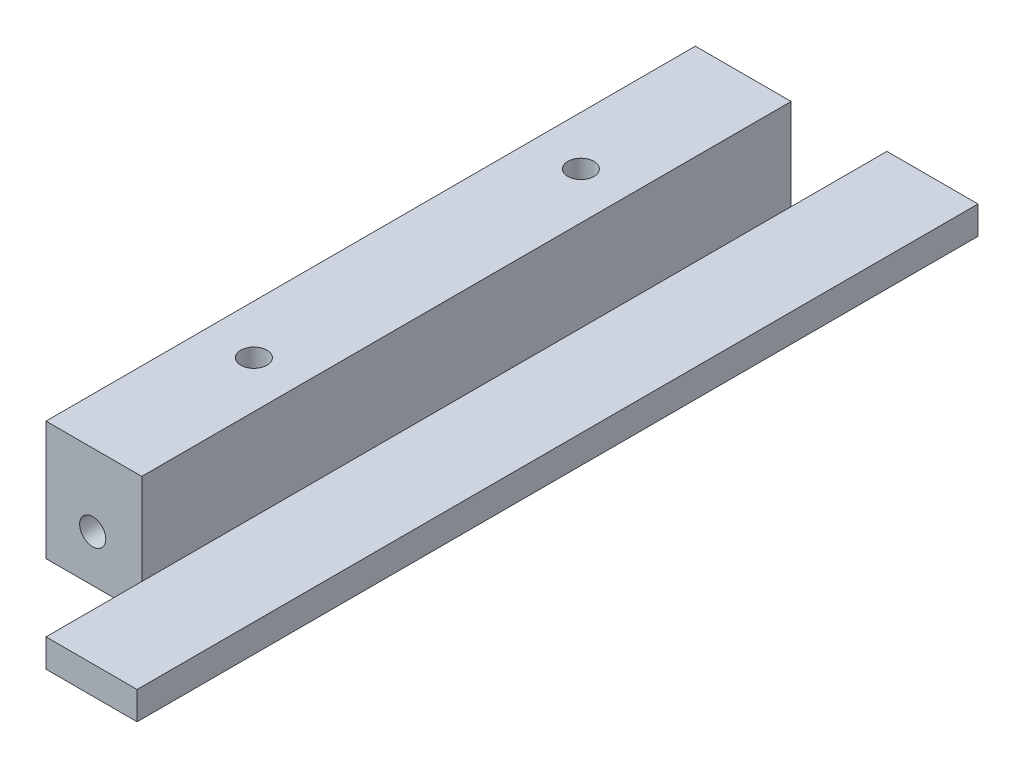
SolidWorks part; units mm, degrees
ref_plane "Płaszczyzna przednia" through (0, 0, 0) normal (0, 0, 1) x (1, 0, 0)
ref_plane "Płaszczyzna górna" through (0, 0, 0) normal (0, 1, 0) x (1, 0, 0)
ref_plane "Płaszczyzna prawa" through (0, 0, 0) normal (1, 0, 0) x (0, 0, -1)
sketch "Szkic1" plane through (0, 0, 0) normal (0, 0, 1) x (1, 0, 0)
  line L0 (9.75, -9.75) -> (9.75, -15.75)
  line L1 (-9.75, -9.75) -> (9.75, -9.75)
  line L2 (-9.75, -9.75) -> (-9.75, 9.75)
  line L3 (-9.75, 9.75) -> (9.75, 9.75)
  line L4 (9.75, -9.75) -> (9.75, 9.75)
  line L5 (-9.75, -9.75) -> (9.75, 9.75) construction
  line L6 (-9.75, 9.75) -> (9.75, -9.75) construction
  line L7 (9.75, -15.75) -> (-30.25, -15.75)
  line L8 (-30.25, -15.75) -> (-30.25, 9.75)
  line L9 (-30.25, 9.75) -> (-9.75, 9.75)
  point P0 (0, 0)
  dimension "D1" = 19.5
  dimension "D2" = 40
  dimension "D3" = 6
extrude "Dodanie-wyciągnięcie1" add sketch "Szkic1" along normal blind 180 contours L8 L7 L0 L1 L2 L3 region at (-16.3423, -4.7831, 0)
ref_plane "Płaszczyzna1" through (0, 0, 90) normal (0, 0, 1) x (1, 0, 0)
sketch "Szkic2" plane through (0, 9.75, 0) normal (0, 1, 0) x (1, 0, 0)
  line L1 (-30.25, -180) -> (-9.75, -180)
  line L2 (-30.25, -180) -> (-30.25, -159.5)
  line L3 (-30.25, -159.5) -> (-9.75, -159.5)
  line L4 (-9.75, -180) -> (-9.75, -159.5)
  line L5 (-9.75, -180) -> (-9.75, 0) construction
  dimension "D1" = 20.5
extrude "Wytnij-wyciągnięcie1" cut sketch "Szkic2" against normal through all
mirror "Lustro1" about plane through (0, 0, 90) normal (0, 0, 1) of "Wytnij-wyciągnięcie1"
sketch "Szkic3" plane through (0, 9.75, 0) normal (0, 1, 0) x (1, 0, 0)
  line L0 (-9.75, -159.5) -> (-9.75, -20.5) construction
  line L2 (-9.75, -20.5) -> (-30.25, -20.5) construction
  circle A0 centre (-19.75, -55.5) radius 2.8
  circle A1 centre (-19.75, -125.5) radius 2.8
  dimension "D1" = 5.6
  dimension "D2" = 10
  dimension "D3" = 70
  dimension "D4" = 35
extrude "Wytnij-wyciągnięcie2" cut sketch "Szkic3" against normal blind 10
sketch "Szkic4" plane through (0, 0, 159.5) normal (0, 0, 1) x (1, 0, 0)
  line L1 (-9.75, -15.75) -> (-30.25, -15.75) construction
  line L2 (-30.25, -15.75) -> (-30.25, 9.75) construction
  circle A0 centre (-20.25, -5.75) radius 2.8
  dimension "D1" = 5.6
  dimension "D2" = 10
  dimension "D3" = 10
extrude "Wytnij-wyciągnięcie3" cut sketch "Szkic4" against normal blind 10
mirror "Lustro2" about plane through (0, 0, 90) normal (0, 0, 1) of "Wytnij-wyciągnięcie3"
